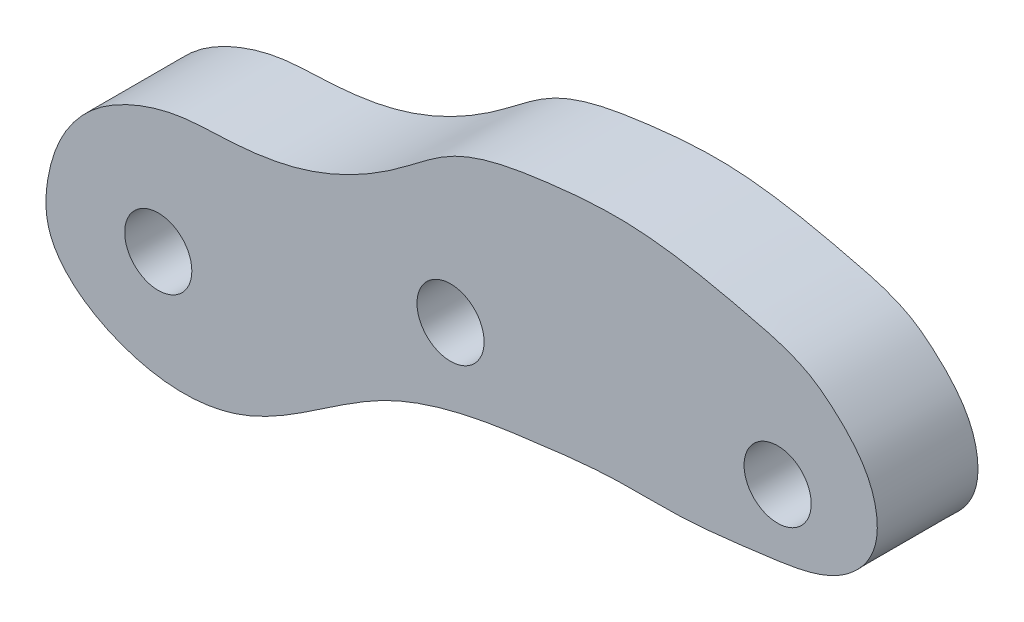
SolidWorks part; units mm, degrees
ref_plane "Спереди" through (0, 0, 0) normal (0, 0, 1) x (1, 0, 0)
ref_plane "Сверху" through (0, 0, 0) normal (0, 1, 0) x (1, 0, 0)
ref_plane "Справа" through (0, 0, 0) normal (1, 0, 0) x (0, 0, -1)
other "Configuration Table"
sketch "Sketch1" plane through (0, 0, 0) normal (0, 0, 1) x (1, 0, 0)
  spline S0 degree 3 poles (-22.4792, 6.3405) (-22.3649, 8.4337) (-21.9598, 9.72) (-21.0622, 10.8254) (-19.8126, 11.558) (-18.4088, 11.9811) (-16.7274, 11.9836) (-14.4302, 12.2981) (-12.2317, 13.4551) (-10.1388, 15.2437) (-7.6727, 15.6872) (-4.66, 15.9527) (-1.9707, 15.3842) (0.1926, 14.8303) (1.3655, 13.8714) (2.3166, 12.8085) (2.5269, 11.0507) (1.1519, 9.5611) (-1.0263, 9.2975) (-3.2788, 8.9877) (-5.5565, 9.0729) (-7.5169, 8.8346) (-9.8066, 8.5304) (-12.1593, 7.8773) (-14.4158, 6.2797) (-16.7729, 4.7959) (-19.8265, 4.6937) (-22.4792, 6.3405) (-22.3649, 8.4337) (-21.9598, 9.72) knots -0.129505 -0.07941 -0.019863 0 0.024708 0.049749 0.071753 0.099215 0.12475 0.158826 0.218727 0.250841 0.300067 0.344427 0.407963 0.442243 0.457874 0.486028 0.514986 0.539924 0.582498 0.624526 0.659072 0.700276 0.726901 0.779346 0.824521 0.870495 0.92059 0.980137 1 1.024708 1.049749 1.071753 only from (-22.3284, 8.3219) to (-22.3284, 8.3219)
  point P8 (-8.4829, 8.7036)
  point P12 (-18.3815, 2.6599)
extrude "Boss-Extrude1" add sketch "Sketch1" along normal blind 3 contours S0
ref_plane "Plane1" through (0, 0, 3) normal (0, 0, 1) x (1, 0, 0)
sketch "Sketch2" plane through (0, 0, 3) normal (0, 0, 1) x (1, 0, 0)
  circle A0 centre (-19.0384, 8.097) radius 1
  circle A1 centre (-10.3315, 10.6213) radius 1
  circle A2 centre (-0.5877, 11.3158) radius 1
  point P4 (0, 0)
  point P5 (0, 0)
  dimension "D1" = 2
extrude "Cut-Extrude1" cut sketch "Sketch2" against normal up to surface (3 mm away) contours A1 | A2 | A0 region at (-10.3315, 10.6213, 3) region at (-0.5877, 11.3158, 3)
equation "\"R small\"= 2"
equation "\"R big\"= 4"
equation "\"width\"= 0.6"
equation "\"border width\"= 1"
equation "\"depth\"= 3"
equation "\"D1@Sketch2\"=\"R small\""
